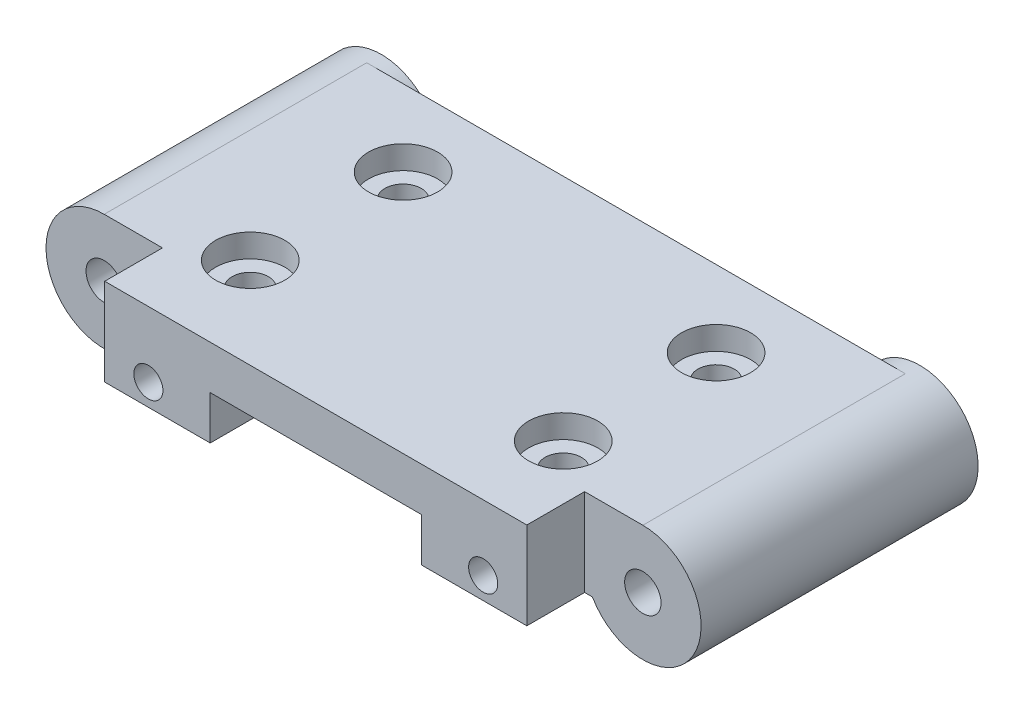
SolidWorks part; units mm, degrees
ref_plane "Front Plane" through (0, 0, 0) normal (0, 0, 1) x (1, 0, 0)
ref_plane "Top Plane" through (0, 0, 0) normal (0, 1, 0) x (1, 0, 0)
ref_plane "Right Plane" through (0, 0, 0) normal (1, 0, 0) x (0, 0, -1)
sketch "Sketch1" plane through (0, 0, 0) normal (0, 0, 1) x (1, 0, 0)
  line L0 (18.5, 3) -> (14.5, 3)
  line L1 (-14.5, -3) -> (14.5, -3)
  line L2 (-14.5, -3) -> (-14.5, 3)
  line L3 (-14.5, 3) -> (14.5, 3)
  line L4 (14.5, -3) -> (14.5, 3)
  line L5 (-14.5, -3) -> (14.5, 3) construction
  line L6 (-14.5, 3) -> (14.5, -3) construction
  line L7 (-14.5, 3) -> (-18.5, 3)
  line L8 (22.5, -1) -> (22.5, -10.2237) construction
  line L9 (-14.5, -3) -> (-15.0359, -3)
  line L10 (14.5, -3) -> (15.0359, -3)
  circle A0 centre (18.5, -1) radius 4
  circle A1 centre (-18.5, -1) radius 4
  point P0 (0, 0)
  dimension "D3" = 8
  dimension "D4" = 8
  dimension "D1" = 29
  dimension "D2" = 6
extrude "Boss-Extrude1" add sketch "Sketch1" along normal blind 22 contours A1 | A1 L2 L7 | A1 L9 L2 | L1 L4 L3 L2 | A0 L4 L10 | A0 | A0 L0 L4 region at (15.3935, 2.1065, 0) region at (18.5, -1, 0) region at (0, 0, 0) region at (14.6587, -2.5069, 0) region at (-15.3935, 2.1065, 0) region at (-18.5, -1, 0) region at (-14.6587, -2.5069, 0)
sketch "Sketch2" plane through (0, 3, 0) normal (0, 1, 0) x (1, 0, 0)
  line L0 (-22.5, 0) -> (-22.5, -22) construction
  line L1 (-22.5, -18.0313) -> (-14.5, -18.0313)
  line L2 (-22.5, -18.0313) -> (-22.5, -22)
  line L3 (-22.5, -22) -> (-14.5, -22)
  line L4 (-14.5, -18.0313) -> (-14.5, -22)
  line L5 (18.5, -22) -> (-18.5, -22) construction
  line L6 (22.5, -22) -> (22.5, 0) construction
  line L7 (22.5, -18.0313) -> (14.5, -18.0313)
  line L8 (22.5, -18.0313) -> (22.5, -22)
  line L9 (22.5, -22) -> (14.5, -22)
  line L10 (14.5, -18.0313) -> (14.5, -22)
  dimension "D1" = 8
  dimension "D2" = 8
  dimension "D3" = 3.9688
extrude "Cut-Extrude1" cut sketch "Sketch2" against normal through all
sketch "Sketch3" plane through (0, 0, 0) normal (0, 0, -1) x (-1, 0, 0)
  circle A0 centre (-18.5, -1) radius 4
  arc A2 (-18.5, 3) -> (-15.0359, -3) centre (-18.5, -1) ccw construction
  circle A3 centre (18.5, -1) radius 4
  arc A4 (15.0359, -3) -> (18.5, 3) centre (18.5, -1) ccw construction
extrude "Boss-Extrude2" add sketch "Sketch3" along normal blind 1
sketch "Sketch4" plane through (0, 0, -1) normal (0, 0, -1) x (-1, 0, 0)
  circle A0 centre (-18.5, -1) radius 1.25
  circle A1 centre (18.5, -1) radius 1.25
  arc A2 (18.5, 3) -> (15.0359, -3) centre (18.5, -1) ccw construction
  circle A3 centre (-18.5, -1) radius 4 construction
  dimension "D1" = 2.5
  dimension "D2" = 2.5
extrude "Cut-Extrude2" cut sketch "Sketch4" against normal through all
sketch "Sketch5" plane through (0, 3, 0) normal (0, 1, 0) x (1, 0, 0)
  line L0 (-12, -5.25) -> (-12, -15.75) construction
  line L1 (-10.75, -17) -> (10.75, -17) construction
  line L2 (12, -15.75) -> (12, -5.25) construction
  line L3 (10.75, -4) -> (-10.75, -4) construction
  line L4 (14.5, -22) -> (-14.5, -22) construction
  line L5 (18.5, 0) -> (-18.5, 0) construction
  line L6 (0, -4) -> (0, -5.8175) construction
  line L7 (0, 0) -> (0, -1.5123) construction
  circle A0 centre (-10.75, -5.25) radius 1.25
  circle A1 centre (10.75, -5.25) radius 1.25
  circle A2 centre (10.75, -15.75) radius 1.25
  circle A3 centre (-10.75, -15.75) radius 1.25
  dimension "D1" = 2.5
  dimension "D2" = 2.5
  dimension "D3" = 2.5
  dimension "D4" = 2.5
  dimension "D5" = 5
  dimension "D6" = 4
  dimension "D7" = 24
extrude "Cut-Extrude3" cut sketch "Sketch5" against normal through all
sketch "Sketch6" plane through (0, -3, 0) normal (0, -1, 0) x (1, 0, 0)
  line L0 (-6.8529, 2) -> (6.8529, 2)
  line L1 (15.0359, 0) -> (-15.0359, 0) construction
  line L2 (-14, 11.8529) -> (-14, 9.1471)
  line L3 (-22.5, 18.0313) -> (-22.5, -1) construction
  line L4 (14, 11.8529) -> (14, 9.1471)
  line L5 (-7.25, 15.75) -> (-7.25, 22)
  line L6 (14.5, 22) -> (-14.5, 22) construction
  line L7 (7.25, 15.75) -> (7.25, 22)
  line L8 (7.25, 22) -> (-7.25, 22)
  line L9 (-14, 12.0678) -> (14, 12.0678) construction
  line L10 (0, 0) -> (0, 12.0678) construction
  arc A0 (-12.5, 12.7189) -> (-7.25, 15.75) centre (-10.75, 15.75) ccw
  arc A1 (7.25, 15.75) -> (12.5, 12.7189) centre (10.75, 15.75) ccw
  arc A2 (12.5, 8.2811) -> (7.7189, 3.5) centre (10.75, 5.25) ccw
  arc A3 (-7.7189, 3.5) -> (-12.5, 8.2811) centre (-10.75, 5.25) ccw
  arc A4 (-14, 11.8529) -> (-12.5, 12.7189) centre (-13, 11.8529) cw
  arc A5 (12.5, 12.7189) -> (14, 11.8529) centre (13, 11.8529) cw
  arc A6 (14, 9.1471) -> (12.5, 8.2811) centre (13, 9.1471) cw
  arc A7 (7.7189, 3.5) -> (6.8529, 2) centre (6.8529, 3) cw
  arc A8 (-6.8529, 2) -> (-7.7189, 3.5) centre (-6.8529, 3) cw
  arc A9 (-12.5, 8.2811) -> (-14, 9.1471) centre (-13, 9.1471) cw
  dimension "D1" = 7
  dimension "D2" = 7
  dimension "D3" = 7
  dimension "D4" = 7
  dimension "D7" = 1
  dimension "D5" = 2
  dimension "D6" = 8.5
extrude "Cut-Extrude4" cut sketch "Sketch6" against normal blind 3
sketch "Sketch7" plane through (0, 0, 22) normal (0, 0, 1) x (1, 0, 0)
  line L0 (-11.5, -2.5) -> (11.5, -2.5) construction
  line L1 (14.5, -3) -> (7.25, -3) construction
  line L2 (0, -2.5) -> (0, 0) construction
  line L3 (-14.5, -3) -> (-14.5, 3) construction
  circle A0 centre (-11.5, -1.5) radius 1
  circle A1 centre (11.5, -1.5) radius 1
  dimension "D1" = 2
  dimension "D2" = 2
  dimension "D3" = 0.5
  dimension "D4" = 3
extrude "Cut-Extrude5" cut sketch "Sketch7" against normal blind 4
sketch "Sketch8" plane through (0, 3, 0) normal (0, 1, 0) x (1, 0, 0)
  circle A0 centre (-10.75, -5.25) radius 2.375
  circle A1 centre (10.75, -5.25) radius 2.375
  circle A2 centre (10.75, -15.75) radius 2.375
  circle A3 centre (-10.75, -15.75) radius 2.375
  dimension "D1" = 4.75
  dimension "D2" = 4.75
  dimension "D3" = 4.75
  dimension "D4" = 4.75
extrude "Cut-Extrude6" cut sketch "Sketch8" against normal blind 1.6
ref_axis "Axis1" through (10.75, -3, 15.75) along (0, 1, 0)
ref_axis "Axis2" through (-10.75, -3, 15.75) along (0, 1, 0)
ref_plane "Plane1" through (0, 0, 15.75) normal (0, 0, -1) x (-1, 0, 0)
ref_axis "Axis3" through (-11.5, -1.5, 18) along (0, 0, 1)
ref_axis "Axis4" through (11.5, -1.5, 18) along (0, 0, 1)
ref_plane "Plane2" through (0, -1.5, 0) normal (0, -1, 0) x (-1, 0, 0)
